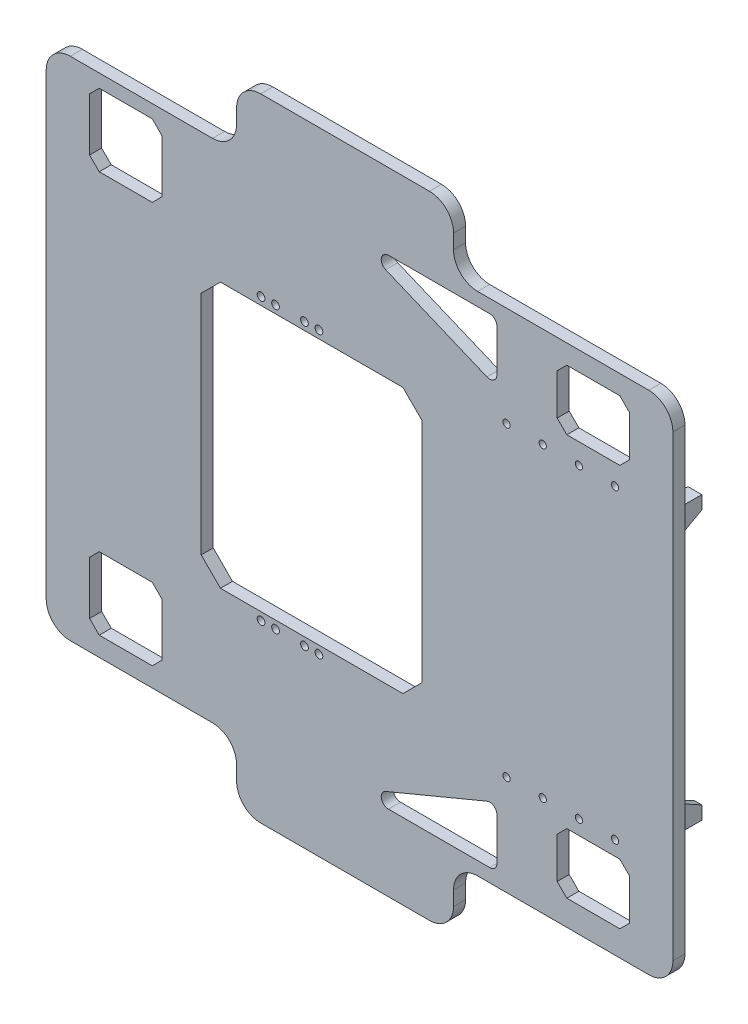
SolidWorks part; units mm, degrees
ref_plane "前视基准面" through (0, 0, 0) normal (0, 0, 1) x (1, 0, 0)
ref_plane "上视基准面" through (0, 0, 0) normal (0, 1, 0) x (1, 0, 0)
ref_plane "右视基准面" through (0, 0, 0) normal (1, 0, 0) x (0, 0, -1)
sketch "草图1" plane through (0, 0, 0) normal (0, 0, 1) x (1, 0, 0)
  line L0 (-51, 115) -> (-51, 121)
  line L1 (-120, 105) -> (-61, 105)
  line L2 (-130, 95) -> (-130, -95)
  line L3 (-120, -105) -> (-61, -105)
  line L4 (130, 95) -> (130, -95)
  line L5 (-130, 105) -> (-126.7518, 102.3765) construction
  line L6 (-130, -105) -> (-126.7518, -102.3765) construction
  line L7 (-41, 131) -> (29, 131)
  line L8 (39, 121) -> (39, 115)
  line L9 (-51, -115) -> (-51, -121)
  line L10 (-41, -131) -> (29, -131)
  line L11 (39, -121) -> (39, -115)
  line L12 (49, 105) -> (120, 105)
  line L13 (49, -105) -> (120, -105)
  line L14 (126.7518, -102.3765) -> (130, -105) construction
  line L15 (126.7518, 102.3765) -> (130, 105) construction
  arc A0 (-130, 95) -> (-120, 105) centre (-120, 95) cw
  arc A1 (-120, -105) -> (-130, -95) centre (-120, -95) cw
  arc A2 (130, 95) -> (120, 105) centre (120, 95) ccw
  arc A3 (120, -105) -> (130, -95) centre (120, -95) ccw
  arc A4 (-61, 105) -> (-51, 115) centre (-61, 115) ccw
  arc A5 (49, 105) -> (39, 115) centre (49, 115) cw
  arc A6 (-41, 131) -> (-51, 121) centre (-41, 121) ccw
  arc A7 (39, 121) -> (29, 131) centre (29, 121) ccw
  arc A8 (-51, -115) -> (-61, -105) centre (-61, -115) ccw
  arc A9 (39, -115) -> (49, -105) centre (49, -115) cw
  arc A10 (-41, -131) -> (-51, -121) centre (-41, -121) cw
  arc A11 (29, -131) -> (39, -121) centre (29, -121) ccw
  point P0 (0, 0)
  point P28 (-45.35, 105)
  point P32 (39, 105)
  point P40 (39, -105)
  dimension "D1" = 10
  dimension "D2" = 10
  dimension "D3" = 10
  dimension "D4" = 10
  dimension "D5" = 10
  dimension "D6" = 10
  dimension "D9" = 10
  dimension "D11" = 10
  dimension "D7" = 10
  dimension "D8" = 10
  dimension "D10" = 10
  dimension "D12" = 10
  dimension "D13" = 210
  dimension "D14" = 59
  dimension "D15" = 71
  dimension "D16" = 59
  dimension "D17" = 71
  dimension "D18" = 70
  dimension "D19" = 6
  dimension "D20" = 6
extrude "凸台-拉伸1" add sketch "草图1" along normal blind 5
sketch "草图2" plane through (0, 0, 5) normal (0, 0, 1) x (1, 0, 0)
  line L0 (130, -95) -> (130, 95) construction
  line L5 (10.8462, -93.7308) -> (52.8462, -76.2308)
  line L6 (-108, 99.5) -> (-86, 99.5)
  line L7 (-108, -67) -> (-86, -67)
  line L8 (-112, -71) -> (-112, -93)
  line L9 (-108, -97) -> (-86, -97)
  line L10 (-82, -71) -> (-82, -93)
  line L11 (-112, -67) -> (-82, -97) construction
  line L12 (-112, -97) -> (-82, -67) construction
  line L13 (86, 97) -> (108, 97)
  line L14 (82, 93) -> (82, 76)
  line L15 (86, 72) -> (108, 72)
  line L16 (112, 93) -> (112, 76)
  line L17 (82, 97) -> (112, 72) construction
  line L18 (82, 72) -> (112, 97) construction
  line L19 (86, -69.5) -> (108, -69.5)
  line L20 (82, -73.5) -> (82, -90.5)
  line L21 (86, -94.5) -> (108, -94.5)
  line L22 (112, -73.5) -> (112, -90.5)
  line L23 (82, -69.5) -> (112, -94.5) construction
  line L24 (82, -94.5) -> (112, -69.5) construction
  line L25 (12, 99.5) -> (54, 99.5)
  line L28 (57, 96.5) -> (57, 79)
  line L29 (10.8462, 93.7308) -> (52.8462, 76.2308)
  line L33 (12, -99.5) -> (54, -99.5)
  line L34 (57, -79) -> (57, -96.5)
  line L35 (-41, -131) -> (29, -131) construction
  line L37 (-112, 95.5) -> (-112, 73.5)
  line L38 (-120, -105) -> (-61, -105) construction
  line L39 (-130, 95) -> (-130, -95) construction
  line L40 (-108, 69.5) -> (-86, 69.5)
  line L41 (-82, 95.5) -> (-82, 73.5)
  line L42 (-112, 99.5) -> (-82, 69.5) construction
  line L43 (-112, 69.5) -> (-82, 99.5) construction
  line L44 (-112, 73.5) -> (-108, 69.5)
  line L45 (-112, 95.5) -> (-108, 99.5)
  line L46 (-86, 69.5) -> (-82, 73.5)
  line L47 (-86, 99.5) -> (-82, 95.5)
  line L48 (-108, -67) -> (-112, -71)
  line L49 (-112, -93) -> (-108, -97)
  line L50 (-86, -67) -> (-82, -71)
  line L51 (-86, -97) -> (-82, -93)
  line L52 (86, 97) -> (82, 93)
  line L53 (82, 76) -> (86, 72)
  line L54 (108, 97) -> (112, 93)
  line L55 (108, 72) -> (112, 76)
  line L56 (86, -69.5) -> (82, -73.5)
  line L57 (108, -69.5) -> (112, -73.5)
  line L58 (82, -90.5) -> (86, -94.5)
  line L59 (108, -94.5) -> (112, -90.5)
  arc A0 (57, -96.5) -> (54, -99.5) centre (54, -96.5) cw
  arc A1 (57, -79) -> (52.8462, -76.2308) centre (54, -79) ccw
  arc A2 (12, -99.5) -> (10.8462, -93.7308) centre (12, -96.5) cw
  arc A3 (10.8462, 93.7308) -> (12, 99.5) centre (12, 96.5) cw
  arc A4 (57, 96.5) -> (54, 99.5) centre (54, 96.5) ccw
  arc A5 (57, 79) -> (52.8462, 76.2308) centre (54, 79) cw
  point P0 (-97, 84.5)
  point P1 (-97, 84.5)
  point P5 (-97, -82)
  point P10 (97, 84.5)
  point P15 (97, -82)
  point P20 (27, 84.5)
  point P25 (27, -82)
  point P75 (-3, 99.5)
  point P78 (57, 99.5)
  dimension "D11" = 3
  dimension "D17" = 3
  dimension "D18" = 3
  dimension "D35" = 3
  dimension "D36" = 3
  dimension "D37" = 3
  dimension "D2" = 8
  dimension "D3" = 18
  dimension "D4" = 30
  dimension "D5" = 25
  dimension "D6" = 30
  dimension "D7" = 18
  dimension "D8" = 18
  dimension "D9" = 25
  dimension "D10" = 30
  dimension "D12" = 60
  dimension "D13" = 25
  dimension "D14" = 30
  dimension "D15" = 25
  dimension "D19" = 42
  dimension "D20" = 17.5
  dimension "D38" = 17.5
  dimension "D39" = 31.5
extrude "切除-拉伸1" cut sketch "草图2" against normal through all
sketch "草图3" plane through (0, 0, 0) normal (0, 0, -1) x (-1, 0, 0)
  line L0 (130, 95) -> (130, -95) construction
  line L1 (57.7, 55) -> (-18, 55)
  line L2 (65.7, 47) -> (65.7, -47)
  line L3 (57.7, -55) -> (-18, -55)
  line L4 (-26, 47) -> (-26, -47)
  line L5 (65.7, 55) -> (-26, -55) construction
  line L6 (65.7, -55) -> (-26, 55) construction
  line L7 (-26, -47) -> (-18, -55)
  line L8 (-18, 55) -> (-26, 47)
  line L9 (65.7, -47) -> (57.7, -55)
  line L10 (57.7, 55) -> (65.7, 47)
  point P0 (19.85, 0)
  dimension "D1" = 64.3
  dimension "D2" = 91.7
  dimension "D3" = 110
extrude "切除-拉伸2" cut sketch "草图3" against normal through all
sketch "草图4" plane through (0, 0, 0) normal (0, 0, -1) x (-1, 0, 0)
  line L0 (-46, -47.5) -> (-46, -58.5)
  line L1 (-46, -58.5) -> (-57, -58.5)
  line L2 (-57, -58.5) -> (-57, -55.5)
  line L3 (-57, -55.5) -> (-49, -55.5)
  line L4 (-49, -55.5) -> (-49, -47.5)
  line L5 (-49, -47.5) -> (-46, -47.5)
  line L6 (-26, 47) -> (-26, -47) construction
  line L8 (-26, 0) -> (-130, 0) construction
  line L9 (-26, 47) -> (-26, -47) construction
  line L10 (-130, -95) -> (-130, 95) construction
  dimension "D1" = 11
  dimension "D2" = 11
  dimension "D3" = 3
  dimension "D4" = 3
  dimension "D5" = 20
  dimension "D6" = 55.5
extrude "凸台-拉伸2" add sketch "草图4" along normal blind 15
sketch "草图5" plane through (0, -58.5, 0) normal (0, -1, 0) x (1, 0, 0)
  line L0 (57, -5) -> (51.5, -15)
  line L1 (57, -15) -> (57, 0) construction
  line L2 (57, -15) -> (46, -15) construction
  line L3 (51.5, -15) -> (57, -15)
  line L4 (57, -15) -> (57, -5)
  dimension "D1" = 10
  dimension "D2" = 5.5
extrude "切除-拉伸3" cut sketch "草图5" against normal blind 10
sketch "草图6" plane through (46, 0, 0) normal (-1, 0, 0) x (0, 0, 1)
  line L0 (-15, -53) -> (-5, -47.5)
  line L1 (-15, -58.5) -> (-15, -47.5) construction
  line L2 (-15, -47.5) -> (0, -47.5) construction
  line L3 (-5, -47.5) -> (-15, -47.5)
  line L4 (-15, -47.5) -> (-15, -53)
  dimension "D1" = 10
  dimension "D2" = 5.5
extrude "切除-拉伸4" cut sketch "草图6" against normal blind 10
ref_plane "基准面2" through (84, 0, 0) normal (1, 0, 0) x (0, 0, -1)
mirror "镜向1" about plane through (84, 0, 0) normal (1, 0, 0) of "凸台-拉伸2", "切除-拉伸4", "切除-拉伸3"
mirror "镜向2" about plane through (0, 0, 0) normal (0, 1, 0) of "镜向1"
sketch "草图7" plane through (0, 0, 0) normal (0, 0, -1) x (-1, 0, 0)
  line L0 (65.7, -47) -> (65.7, 47) construction
  line L1 (-18, -55) -> (57.7, -55) construction
  circle A0 centre (16.85, -58.25) radius 1.6
  circle A1 centre (22.85, -58.25) radius 1.6
  circle A2 centre (40.85, -58.25) radius 1.6
  circle A3 centre (34.85, -58.25) radius 1.6
  dimension "D1" = 3.2
  dimension "D2" = 3.2
  dimension "D3" = 3.2
  dimension "D4" = 3.2
  dimension "D6" = 6
  dimension "D7" = 6
  dimension "D8" = 30.85
  dimension "D9" = 3.25
  dimension "D5" = 18
extrude "切除-拉伸5" cut sketch "草图7" against normal through all
mirror "镜向3" about plane through (0, 0, 0) normal (0, 1, 0) of "切除-拉伸5"
sketch "草图8" plane through (0, 0, 0) normal (0, 0, -1) x (-1, 0, 0)
  line L0 (-46, -58.5) -> (-46, -53) construction
  line L2 (-57, -55.5) -> (-51.5, -55.5) construction
  line L3 (-130, 0) -> (-26, 0) construction
  line L4 (-130, -95) -> (-130, 95) construction
  line L5 (-26, 47) -> (-26, -47) construction
  circle A0 centre (-61, -63.5) radius 1.5
  circle A4 centre (-76, -63.5) radius 1.5
  circle A5 centre (-91, -63.5) radius 1.5
  circle A6 centre (-106, -63.5) radius 1.5
  circle A7 centre (-106, 63.5) radius 1.5
  circle A8 centre (-91, 63.5) radius 1.5
  circle A9 centre (-76, 63.5) radius 1.5
  circle A10 centre (-61, 63.5) radius 1.5
  dimension "D1" = 4
  dimension "D2" = 3
  dimension "D3" = 15
  dimension "D4" = 8
extrude "切除-拉伸6" cut sketch "草图8" against normal through all
equation "\"45、\"=43.7672"
